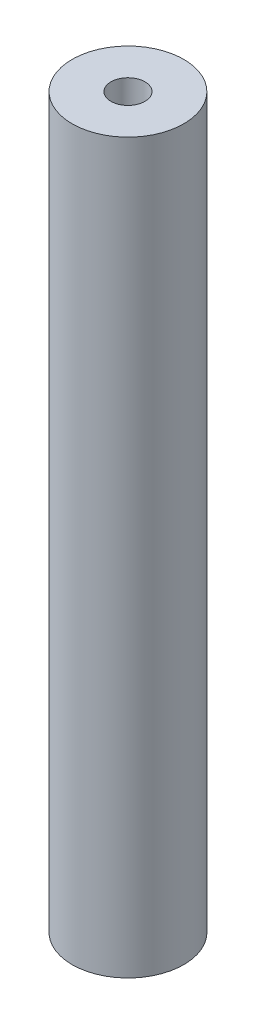
SolidWorks part; units mm, degrees
material "PVC Rígido"
ref_plane "Plano frontal" through (0, 0, 0) normal (0, 0, 1) x (1, 0, 0)
ref_plane "Plano superior" through (0, 0, 0) normal (0, 1, 0) x (1, 0, 0)
ref_plane "Plano direito" through (0, 0, 0) normal (1, 0, 0) x (0, 0, -1)
sketch "Esboço1" plane through (0, 0, 0) normal (0, 1, 0) x (1, 0, 0)
  line L0 (0, 0) -> (-14.05, 0) construction
  line L1 (-14.1591, 1.997) -> (-2.2091, 2.65)
  line L2 (-2.2091, -2.65) -> (-14.1591, -1.997)
  arc A0 (-2.2091, -2.65) -> (-2.2091, 2.65) centre (0, 0) ccw
  arc A1 (-14.1591, 1.997) -> (-14.1591, -1.997) centre (-14.05, 0) ccw
  dimension "D1" = 6.9
  dimension "D2" = 4
  dimension "D3" = 19.5
  dimension "D4" = 5.3
extrude "Ressalto-extrusão1" add sketch "Esboço1" against normal blind 1.4
sketch "Esboço2" plane through (0, -1.4, 0) normal (0, -1, 0) x (1, 0, 0)
  arc A0 (-2.2091, -2.65) -> (-2.2091, 2.65) centre (0, 0) ccw construction
  circle A1 centre (0, 0) radius 3.45
extrude "Ressalto-extrusão2" add sketch "Esboço2" along normal offset from surface (2.4 mm away) 3.8 up to face at (-7.242, 0, 0)
hole_wizard "Furo4" positions "Esboço9" profile "Esboço10" legacy end condition through all
sketch "Esboço9" plane through (0, 0, 0) normal (0, 1, 0) x (1, 0, 0)
  line L1 (-14.45, 0) -> (0, 0) construction
  arc A2 (-14.1591, 1.997) -> (-14.1591, -1.997) centre (-14.05, 0) ccw construction
  point P0 (-14.45, 0)
  point P19 (-16.05, 0)
  dimension "D1" = 1.6
sketch "Esboço10" plane through (-14.45, 0, 0) normal (1, 0, 0) x (0, 0, 1)
  line L0 (0, 0) -> (0, 3.8)
  line L1 (0, 3.8) -> (0.6, 3.8)
  line L2 (0.6, 3.8) -> (0.6, 0)
  line L3 (0.6, 0) -> (0, 0)
  line L4 (0, 110) -> (0, -10) construction
  dimension "Diameter" = 1.2
  dimension "Depth" = 3.8
pattern_linear "Padrão linear1" count 6 spacing 2 along (1, 0, 0) of "Furo4"
hole_wizard "Furo1" positions "Esboço3" profile "Esboço4" legacy
sketch "Esboço3" plane through (0, -3.8, 0) normal (0, -1, 0) x (-1, 0, 0)
  point P0 (0, 0)
sketch "Esboço4" plane through (0, -3.8, 0) normal (1, 0, 0) x (0, 0, -1)
  line L0 (0, 0) -> (0, 2)
  line L1 (0, 2) -> (2.475, 2)
  line L2 (2.475, 2) -> (2.475, 0)
  line L3 (2.475, 0) -> (0, 0)
  line L4 (0, 110) -> (0, -10) construction
  dimension "Diameter" = 4.95
  dimension "Depth" = 2
hole_wizard "Furo2" positions "Esboço5" profile "Esboço6" legacy
sketch "Esboço5" plane through (0, 0, 0) normal (0, 1, 0) x (1, 0, 0)
  point P0 (0, 0)
sketch "Esboço6" plane through (0, 0, 0) normal (1, 0, 0) x (0, 0, 1)
  line L0 (0, 0) -> (0, 1)
  line L1 (0, 1) -> (2.3, 1)
  line L2 (2.3, 1) -> (2.3, 0)
  line L3 (2.3, 0) -> (0, 0)
  line L4 (0, 110) -> (0, -10) construction
  dimension "Diameter" = 4.6
  dimension "Depth" = 1
hole_wizard "Furo3" positions "Esboço7" profile "Esboço8" legacy end condition through all
sketch "Esboço7" plane through (0, 0, 0) normal (0, 1, 0) x (1, 0, 0)
  point P0 (0, 0)
sketch "Esboço8" plane through (0, 0, 0) normal (1, 0, 0) x (0, 0, 1)
  line L0 (0, 0) -> (0, 3.8)
  line L1 (0, 3.8) -> (1.05, 3.8)
  line L2 (1.05, 3.8) -> (1.05, 0)
  line L3 (1.05, 0) -> (0, 0)
  line L4 (0, 110) -> (0, -10) construction
  dimension "Diameter" = 2.1
  dimension "Depth" = 3.8
sketch "Esboço11" plane through (0, -3.8, 0) normal (0, -1, 0) x (1, 0, 0)
  line L0 (-0.0981, 2.4731) -> (0, 2.375)
  line L1 (0, 2.375) -> (0.0981, 2.4731)
  line L2 (0, 0) -> (0, 2.475) construction
  circle A0 centre (0, 0) radius 2.375 construction
  circle A1 centre (0, 0) radius 2.475
  arc A2 (0.0981, 2.4731) -> (-0.0981, 2.4731) centre (0, 0) ccw
  dimension "D3" = 4.75
  dimension "D2" = 0.1
  dimension "D1" = 0
extrude "Ressalto-extrusão3" add sketch "Esboço11" against normal up to surface (2 mm away) up to face at (0, -1.8, 1.05)
pattern_circular "PadrãoCircular1" count 60 over 360 about axis through (0, -1.4, 0) along (0, 1, 0) of "Ressalto-extrusão3"
sketch "Sketch1" plane through (0, -3.8, 0) normal (0, -1, 0) x (1, 0, 0)
  line L0 (0, 3.45) -> (-16.05, 3.45)
  line L5 (-16.05, 3.45) -> (-16.05, -3.45)
  line L6 (-16.05, -3.45) -> (0, -3.45)
  line L7 (0, 3.45) -> (0, -3.45) construction
  arc A2 (-14.1591, 1.997) -> (-14.1591, -1.997) centre (-14.05, 0) ccw construction
  arc A3 (0, 3.45) -> (0, -3.45) centre (0, 0) ccw
  circle A4 centre (0, 0) radius 3.45 construction
  point P2 (0, 0)
  point P7 (0, 0)
extrude "Cut-Extrude3" cut sketch "Sketch1" against normal through all
sketch "Sketch3" plane through (0, -1, 0) normal (0, 1, 0) x (1, 0, 0)
  circle A0 centre (0, 0) radius 3.45
  circle A1 centre (0, 0) radius 1.05
  dimension "D1" = 6.9
  dimension "D2" = 2.1
extrude "Boss-Extrude1" add sketch "Sketch3" along normal blind 42.2
